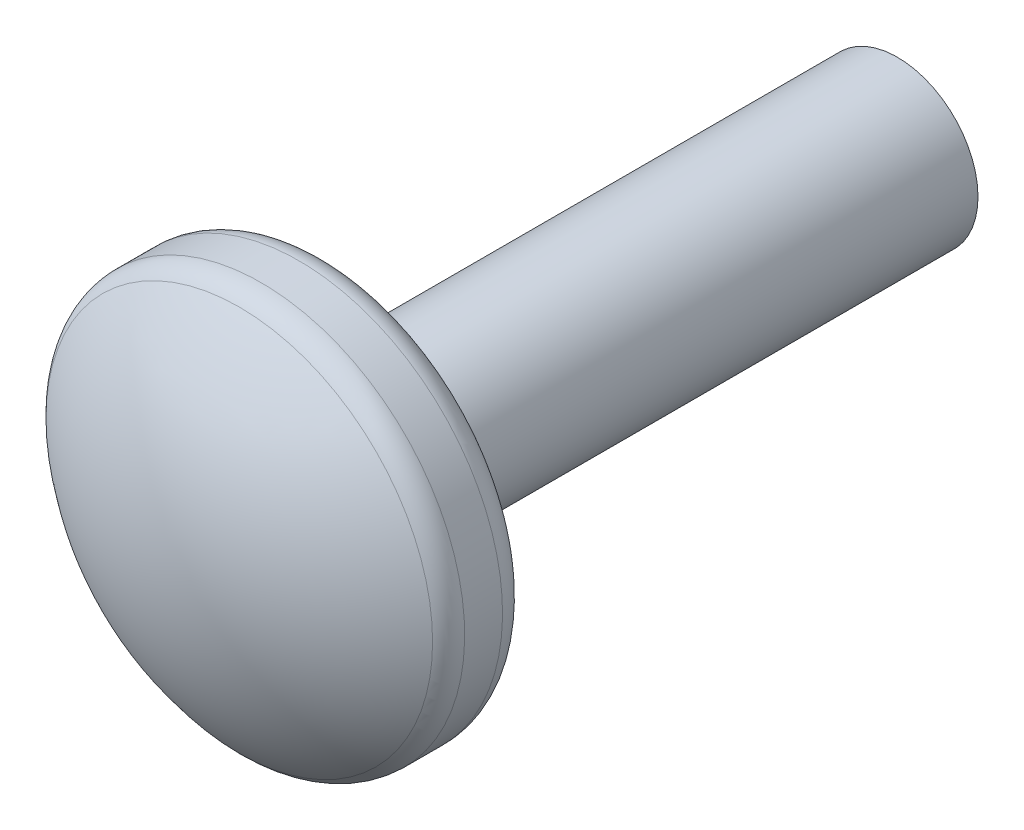
SolidWorks part; units mm, degrees
ref_plane "Front Plane" through (0, 0, 0) normal (0, 0, 1) x (1, 0, 0)
ref_plane "Top Plane" through (0, 0, 0) normal (0, 1, 0) x (1, 0, 0)
ref_plane "Right Plane" through (0, 0, 0) normal (1, 0, 0) x (0, 0, -1)
sketch "Sketch1" plane through (0, 0, 0) normal (0, 0, 1) x (1, 0, 0)
  circle A0 centre (0, 0) radius 2.5
  dimension "decimal equ" = 5
curve "Helix/Spiral1" pitch 0.8 height 14.8 turns 18.5 parameters "helix length"=14.8, "pitch"=0.8
sketch "Sketch2" plane through (0, 0, 0) normal (1, 0, 0) x (0, 0, -1)
  line L0 (-0.05, 2.5) -> (0.05, 2.5)
  line L1 (0.05, 2.5) -> (0.35, 1.9804)
  line L2 (-0.05, 2.5) -> (-0.35, 1.9804)
  line L3 (-0.35, 1.9804) -> (0.35, 1.9804)
  line L4 (0, 0) -> (0, 2.5) construction
  line L5 (0, 2.5) -> (0, -2.5) construction
  line L6 (-0.2, 2.2402) -> (0.2, 2.2402) construction
  dimension "D1" = 60
  dimension "D2" = 30
  dimension "D3" = 0.1
  dimension "D4" = 0.4
sketch "Sketch3" plane through (0, 0, 0) normal (1, 0, 0) x (0, 0, -1)
  line L0 (0, 0) -> (2.3536, 0) construction
  line L1 (-0.35, 1.9804) -> (0.35, 1.9804) construction
  line L2 (0, 0) -> (-14, 0)
  line L3 (0, 0) -> (0, 1.9804)
  line L4 (0, 1.9804) -> (-14, 1.9804)
  line L5 (-14, 0) -> (-14, 1.9804)
  dimension "length" = 14
revolve "Revolve1" add sketch "Sketch3" angle 360 about L0
sweep "Sweep1" [suppressed] add profiles "Sketch2" path "Helix/Spiral1"
sketch "Sketch6" [suppressed] plane through (0, 0, 0) normal (1, 0, 0) x (0, 0, -1)
  line L5 (-0.05, 2.5) -> (-0.35, 1.9804)
  line L6 (-0.35, 1.9804) -> (0, 1.9804)
  line L7 (0, 1.9804) -> (0.35, 1.9804)
  line L8 (0.35, 1.9804) -> (0.05, 2.5)
  line L9 (0.05, 2.5) -> (-0.05, 2.5)
  line L10 (-0.05, 2.5) -> (-0.35, 1.9804)
  line L11 (-0.35, 1.9804) -> (0, 1.9804)
  line L12 (0, 1.9804) -> (0.35, 1.9804)
  line L13 (0.35, 1.9804) -> (0.05, 2.5)
  line L14 (0.05, 2.5) -> (-0.05, 2.5)
  dimension "D1" = 0
sketch "Sketch7" plane through (0, 0, 0) normal (0, 0, 1) x (1, 0, 0)
  circle A1 centre (0, 0) radius 2.5
  circle A2 centre (0, 0) radius 2.5
  dimension "D1" = 0
sketch "Sketch4" plane through (0, 0, 0) normal (1, 0, 0) x (0, 0, -1)
  line L0 (0, 1.9804) -> (-3.175, 5.1554)
  line L1 (2.54, 0) -> (3.8556, 0) construction
  line L2 (-3.175, 5.1554) -> (2.54, 5.1554)
  line L3 (0, 0) -> (0, 1.9804)
  line L4 (0, 0) -> (2.54, 0)
  line L5 (2.54, 0) -> (2.54, 5.1554)
  line L6 (0, 1.9804) -> (-14, 1.9804) construction
  dimension "D1" = 2.54
  dimension "D2" = 45
  dimension "D3" = 3.175
sketch "Sketch10" plane through (0, 0, 0) normal (1, 0, 0) x (0, 0, -1)
  line L0 (0, 0) -> (23.0169, 0) construction
  line L1 (-268, 12.7) -> (-14, 12.7)
  line L2 (-268, 12.7) -> (-268, 0)
  line L3 (-268, 0) -> (-14, 0)
  line L4 (-14, 12.7) -> (-14, 0)
  line L5 (-14, 0) -> (-14, 1.9804) construction
  dimension "D1" = 254
  dimension "D2" = 12.7
ref_plane "Plane3" through (0, 0, 14) normal (0, 0, 1) x (1, 0, 0)
sketch "Sketch8" plane through (0, 0, 0) normal (1, 0, 0) x (0, 0, -1)
  line L0 (0, 0) -> (-6.2449, 0) construction
  line L1 (-17.9, 0) -> (-14, 0)
  line L2 (-17.9, 0) -> (-17.9, 5)
  line L3 (-17.9, 5) -> (-14, 5)
  line L4 (-14, 0) -> (-14, 5)
  line L5 (-17.9, -5) -> (-14, -5) construction
  line L6 (-14, 0) -> (-14, 1.9804) construction
  dimension "head dia" = 10
  dimension "head height" = 3.9
revolve "Revolve2" add sketch "Sketch8" angle 360 about L0
sketch "Sketch11" plane through (0, 0, 0) normal (1, 0, 0) x (0, 0, -1)
  line L0 (-15.95, 5) -> (-15.95, -4.0894) construction
  line L1 (-17.9, 0) -> (-6.8951, 0) construction
  line L2 (-17.9, 5) -> (-14, 5) construction
  line L3 (-17.9, 0) -> (-17.9, 5) construction
  line L4 (-15.6327, 5) -> (-14.702, 5)
  line L6 (-14, 0) -> (-14, 5) construction
  line L7 (-14, 4.298) -> (-13.365, 4.298)
  line L8 (-13.365, 4.298) -> (-13.365, 5.635)
  line L9 (-13.365, 5.635) -> (-18.535, 5.635)
  line L10 (-18.535, 5.635) -> (-18.535, 0)
  line L11 (-18.535, 0) -> (-17.9, 0)
  arc A0 (-16.1702, 4.7495) -> (-17.9, 0) centre (-10.5147, 0) ccw
  arc A1 (-14, 4.298) -> (-14.702, 5) centre (-14.702, 4.298) ccw
  arc A2 (-16.1702, 4.7495) -> (-15.6327, 5) centre (-15.6327, 4.298) cw
  dimension "D1" = 0.702
  dimension "D2" = 0.635
  dimension "D3" = 0.635
  dimension "D4" = 0.635
revolve "Cut-Revolve3" cut sketch "Sketch11" angle 360 about L1
ref_plane "Plane1" through (0, 0, 17.9) normal (0, 0, 1) x (1, 0, 0)
sketch "Sketch12" plane through (0, 0, 17.9) normal (0, 0, 1) x (1, 0, 0)
  line L0 (0.5, 2.4495) -> (0.5, 1.25)
  line L1 (0.5, 1.25) -> (1.25, 0.5) construction
  line L2 (1.25, 0.5) -> (2.4495, 0.5)
  line L3 (0, 2.5) -> (0, 0)
  line L4 (0, 0) -> (2.5, 0)
  line L5 (0, 0) -> (0, 5) construction
  line L6 (0, 0) -> (0.875, 0.875) construction
  line L7 (1.25, 0) -> (1.25, 1.5633) construction
  line L8 (0.5, 1.25) -> (0.7197, 0.7197)
  line L9 (1.25, 0.5) -> (0.7197, 0.7197)
  line L10 (0, 0) -> (0, -1.0114) construction
  line L11 (-0.5, 2.4495) -> (-0.5, 1.25) construction
  arc A0 (2.5, 0) -> (2.4495, 0.5) centre (0, 0) ccw
  arc A1 (0.5, 2.4495) -> (0, 2.5) centre (0, 0) ccw
  arc A2 (-2.5, 0) -> (-2.4495, 0.5) centre (0, 0) cw construction
  dimension "phillips dia" = 5
  dimension "D2" = 45
  dimension "D4" = 22.5
  dimension "slot width" = 1
equation "\"D3@Sketch2\" = \"pitch@Helix/Spiral1\"/8"
equation "\"D4@Sketch2\" = \"pitch@Helix/Spiral1\"/2"
equation "\"D1@Sketch11\"= \"head height@Sketch8\" * .18"
equation "\"helix length@Helix/Spiral1\"= \"length@Sketch3\" + \"pitch@Helix/Spiral1\""
